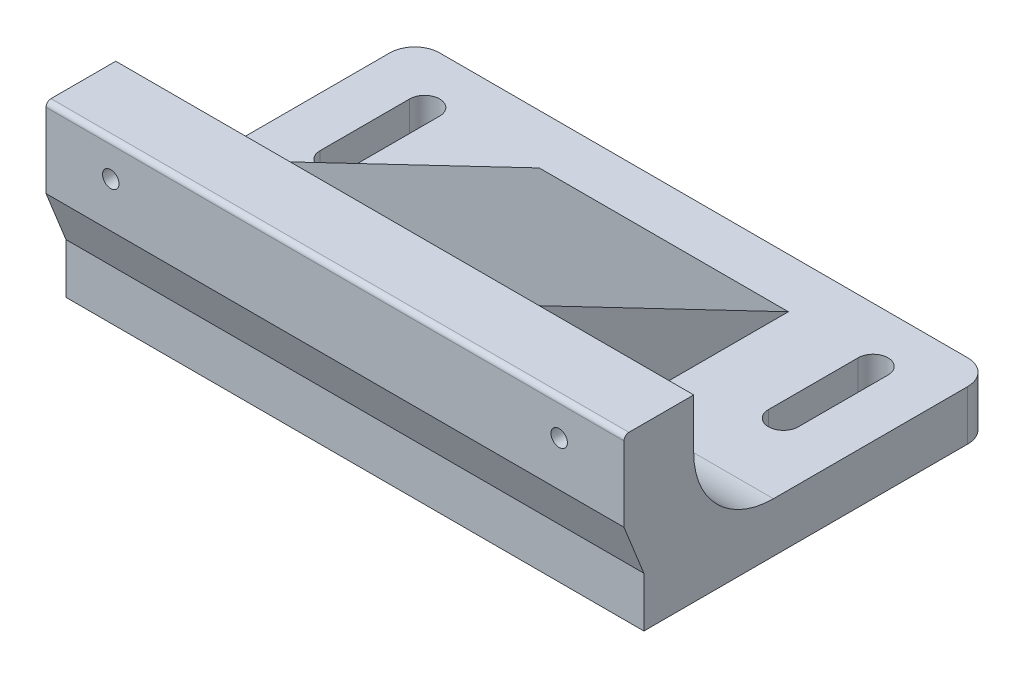
SolidWorks part; units mm, degrees
ref_plane "Front Plane" through (0, 0, 0) normal (0, 0, 1) x (1, 0, 0)
ref_plane "Top Plane" through (0, 0, 0) normal (0, 1, 0) x (1, 0, 0)
ref_plane "Right Plane" through (0, 0, 0) normal (1, 0, 0) x (0, 0, -1)
sketch "Sketch1" plane through (0, 0, 0) normal (0, 1, 0) x (1, 0, 0)
  line L1 (0, 0) -> (116, 0)
  line L2 (0, 0) -> (0, 70)
  line L3 (0, 70) -> (116, 70)
  line L4 (116, 0) -> (116, 70)
  line L5 (0, 0) -> (116, 70) construction
  line L6 (0, 70) -> (116, 0) construction
  point P4 (58, 35)
  dimension "D1" = 70
  dimension "D2" = 116
extrude "Boss-Extrude1" add sketch "Sketch1" along normal blind 10
sketch "Sketch2" plane through (0, 0, 0) normal (0, 0, 1) x (1, 0, 0)
  line L0 (116, 10) -> (116, 0) construction
  line L1 (0, 10) -> (116, 10)
  line L2 (0, 10) -> (0, 19.05)
  line L3 (0, 19.05) -> (116, 19.05)
  line L4 (116, 10) -> (116, 19.05)
  line L5 (0, 10) -> (116, 19.05) construction
  line L6 (0, 19.05) -> (116, 10) construction
  line L7 (0, 0) -> (116, 0) construction
  point P4 (58, 14.525)
  dimension "D1" = 19.05
extrude "Boss-Extrude2" add sketch "Sketch2" against normal blind 10
sketch "Sketch3" plane through (0, 10, 0) normal (0, 1, 0) x (1, 0, 0)
  line L0 (13, 50) -> (103, 50) construction
  line L1 (0, 10) -> (116, 10) construction
  line L2 (58, 10) -> (58, 50) construction
  line L3 (58, 50) -> (58, 70) construction
  line L4 (116, 70) -> (0, 70) construction
  line L5 (13, 59) -> (13, 41) construction
  line L6 (16, 59) -> (16, 41)
  line L7 (10, 59) -> (10, 41)
  line L8 (103, 59) -> (103, 41) construction
  line L9 (100, 59) -> (100, 41)
  line L10 (106, 59) -> (106, 41)
  circle A0 centre (103, 50) radius 3 construction
  circle A1 centre (13, 50) radius 3 construction
  arc A2 (16, 59) -> (10, 59) centre (13, 59) ccw
  arc A3 (10, 41) -> (16, 41) centre (13, 41) ccw
  arc A4 (100, 59) -> (106, 59) centre (103, 59) cw
  arc A5 (106, 41) -> (100, 41) centre (103, 41) cw
  point P4 (58, 10)
  point P5 (58, 50)
  point P14 (13, 50)
  point P24 (103, 50)
  dimension "D1" = 6
  dimension "D2" = 90
  dimension "D3" = 20
  dimension "D4" = 0
  dimension "D5" = 18
extrude "Cut-Extrude1" cut sketch "Sketch3" against normal through all
sketch "Sketch4" plane through (0, 0, 0) normal (0, 0, 1) x (1, 0, 0)
  line L0 (116, 19.05) -> (116, 0) construction
  line L1 (0, 19.05) -> (116, 19.05)
  line L2 (0, 19.05) -> (0, 36.05)
  line L3 (0, 36.05) -> (116, 36.05)
  line L4 (116, 19.05) -> (116, 36.05)
  line L5 (0, 19.05) -> (116, 36.05) construction
  line L6 (0, 36.05) -> (116, 19.05) construction
  point P4 (58, 27.55)
  dimension "D1" = 17
extrude "Boss-Extrude3" add sketch "Sketch4" against normal up to surface (10 mm away) up to face at (58, 14.525, -10)
fillet "Fillet1" radius 16 1 edges at (58, 10, -10)
sketch "Sketch6" plane through (0, 0, 0) normal (-1, 0, 0) x (0, 0, 1)
  line L0 (-60, 10) -> (-10, 36.05)
  line L1 (-70, 10) -> (-26, 10) construction
  line L2 (-10, 36.05) -> (-10, 26) construction
  line L3 (-60, 10) -> (-26, 10)
  line L4 (-10, 36.05) -> (-10, 26)
  line L5 (-60, 10) -> (-60, 36.05) construction
  line L6 (-60, 36.05) -> (-10, 36.05) construction
  line L7 (-10, 36.05) -> (0, 36.05) construction
  arc A0 (-26, 10) -> (-10, 26) centre (-26, 26) ccw construction
  arc A1 (-26, 10) -> (-10, 26) centre (-26, 26) ccw
  point P7 (0, 0)
  line M10 (-10, 36.05) -> (-10, 26)
  arc M11 (-10, 26) -> (-26, 10) centre (-26, 26) cw
  line M12 (-26, 10) -> (-70, 10)
  dimension "D1" = 0
  dimension "D2" = 50
extrude "Boss-Extrude4" add sketch "Sketch6" against normal blind 50 from offset 35 contours L0 M12 M11 M10 region at (0, 19.1541, -27.8729) offset against normal yes
sketch "Sketch7" plane through (0, 0, 0) normal (-1, 0, 0) x (0, 0, 1)
  line L1 (0, 36.05) -> (4, 36.05)
  line L2 (0, 36.05) -> (0, 20.05)
  line L3 (0, 20.05) -> (4, 20.05)
  line L4 (4, 36.05) -> (4, 20.05)
  line L5 (0, 36.05) -> (4, 20.05) construction
  line L6 (0, 20.05) -> (4, 36.05) construction
  point P4 (2, 28.05)
  dimension "D1" = 16
  dimension "D2" = 4
extrude "Boss-Extrude5" add sketch "Sketch7" against normal up to surface (116 mm away) up to face at (116, 16.398, -26.098)
chamfer "Chamfer1" distance 4 distance2 10 1 edges at (58, 20.05, 0) first distance on face at (58, 20.05, 2)
fillet "Fillet3" radius 1 1 edges at (58, 36.05, 4)
fillet "Fillet4" radius 5 2 edges at (0, 5, -70) (116, 5, -70)
sketch "Sketch8" plane through (0, 0, 4) normal (0, 0, 1) x (1, 0, 0)
  line L0 (0, 29.05) -> (116, 29.05) construction
  line L1 (0, 20.05) -> (0, 35.05) construction
  line L2 (116, 35.05) -> (116, 20.05) construction
  line L4 (0, 36.05) -> (116, 36.05) construction
  circle A0 centre (13, 29.05) radius 1.65
  circle A1 centre (103, 29.05) radius 1.65
  circle A2 centre (58, 29.05) radius 1.65 construction
  dimension "D1" = 3.3
  dimension "D2" = 45
  dimension "D3" = 45
  dimension "D4" = 7
extrude "Cut-Extrude2" cut sketch "Sketch8" against normal through all
sketch "Sketch9" plane through (0, 0, -10) normal (0, 0, -1) x (-1, 0, 0)
  circle A0 centre (-103, 29.05) radius 2.25
  circle A1 centre (-13, 29.05) radius 2.25
  dimension "D1" = 4.5
extrude "Cut-Extrude3" cut sketch "Sketch9" against normal blind 5
sketch "Sketch10" plane through (0, 10, 0) normal (0, 1, 0) x (1, 0, 0)
  line L0 (13, 41) -> (13, -4) construction
  line L1 (116, -4) -> (0, -4) construction
